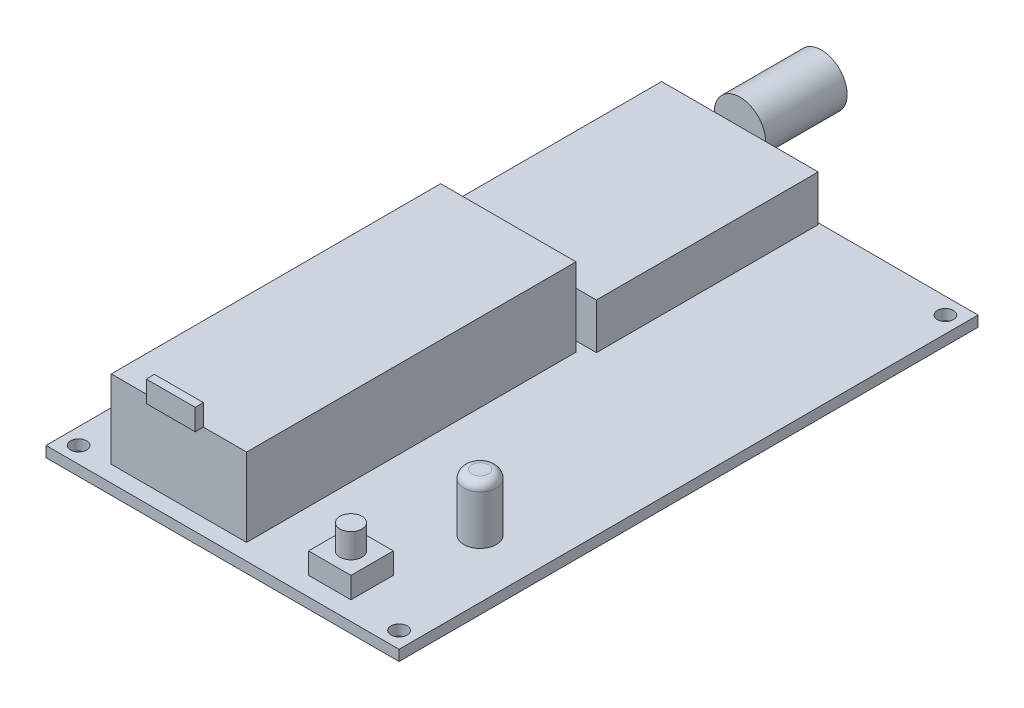
SolidWorks part; units mm, degrees
ref_plane "Front Plane" through (0, 0, 0) normal (0, 0, 1) x (1, 0, 0)
ref_plane "Top Plane" through (0, 0, 0) normal (0, 1, 0) x (1, 0, 0)
ref_plane "Right Plane" through (0, 0, 0) normal (1, 0, 0) x (0, 0, -1)
sketch "Sketch1" plane through (0, 0, 0) normal (0, 1, 0) x (1, 0, 0)
  line L1 (0, 0) -> (54.991, 0)
  line L2 (0, 0) -> (0, 90.17)
  line L3 (0, 90.17) -> (54.991, 90.17)
  line L4 (54.991, 0) -> (54.991, 90.17)
  dimension "D1" = 54.991
  dimension "D2" = 90.17
extrude "Board" add sketch "Sketch1" along normal blind 1.651
sketch "Sketch2" plane through (0, 1.651, 0) normal (0, 1, 0) x (1, 0, 0)
  line L0 (0, 0) -> (54.991, 0) construction
  line L1 (7.62, 2.54) -> (28.702, 2.54)
  line L2 (7.62, 2.54) -> (7.62, 53.848)
  line L3 (7.62, 53.848) -> (28.702, 53.848)
  line L4 (28.702, 2.54) -> (28.702, 53.848)
  line L5 (37.973, 9.525) -> (44.577, 9.525)
  line L6 (37.973, 9.525) -> (37.973, 2.921)
  line L7 (37.973, 2.921) -> (44.577, 2.921)
  line L8 (44.577, 9.525) -> (44.577, 2.921)
  line L9 (54.991, 0) -> (54.991, 90.17) construction
  line L10 (0, 90.17) -> (0, 0) construction
  line L12 (5.969, 89.916) -> (30.353, 89.916)
  line L13 (5.969, 89.916) -> (5.969, 55.372)
  line L14 (5.969, 55.372) -> (30.353, 55.372)
  line L15 (30.353, 89.916) -> (30.353, 55.372)
  point P18 (18.161, 55.372)
  point P19 (18.161, 53.848)
  point P20 (0, 0)
  dimension "D1" = 21.082
  dimension "D2" = 51.308
  dimension "D3" = 6.604
  dimension "D4" = 6.604
  dimension "D5" = 9.525
  dimension "D6" = 17.018
  dimension "D7" = 2.54
  dimension "D8" = 7.62
  dimension "D9" = 24.384
  dimension "D10" = 34.544
  dimension "D11" = 1.524
extrude "RPI" add sketch "Sketch2" along normal blind 12.192 contours L1 L4 L3 L2 region at (18.161, 1.651, -28.194)
extrude "Button Base" add sketch "Sketch2<3>" along normal blind 3.302 contours L6 L7 L8 L5
sketch "Sketch2<3>" plane through (0, 1.651, 0) normal (0, 1, 0) x (1, 0, 0) same geometry as "Sketch2"
extrude "Zigbee" add sketch "Sketch2<4>" along normal blind 7.112 contours L13 L14 L15 L12
sketch "Sketch2<4>" plane through (0, 1.651, 0) normal (0, 1, 0) x (1, 0, 0) same geometry as "Sketch2"
sketch "Sketch3" plane through (0, 4.953, 0) normal (0, 1, 0) x (1, 0, 0)
  line L0 (37.973, 9.525) -> (44.577, 9.525) construction
  line L1 (37.973, 9.525) -> (37.973, 2.921) construction
  circle A0 centre (41.275, 6.223) radius 1.7145
  point P2 (41.275, 9.525)
  point P3 (37.973, 6.223)
  point P6 (0, 0)
  dimension "D1" = 3.429
extrude "Button" add sketch "Sketch3" along normal blind 3.81
sketch "Sketch4" plane through (0, 1.651, 0) normal (0, 1, 0) x (1, 0, 0)
  circle A0 centre (45.9084, 21.7018) radius 2.54
  dimension "D1" = 5.08
extrude "LED" add sketch "Sketch4" along normal blind 8.89
fillet "Fillet1" radius 1.27 1 edges at (45.9084, 10.541, -19.1618)
sketch "Sketch5" plane through (0, 0, -2.54) normal (0, 0, 1) x (1, 0, 0)
  line L0 (7.62, 13.843) -> (28.702, 13.843) construction
  line L1 (21.971, 13.843) -> (14.351, 13.843)
  line L2 (21.971, 13.843) -> (21.971, 17.145)
  line L3 (21.971, 17.145) -> (14.351, 17.145)
  line L4 (14.351, 13.843) -> (14.351, 17.145)
  point P6 (18.161, 13.843)
  point P7 (18.161, 17.145)
  point P8 (0, 0)
  dimension "D1" = 7.62
  dimension "D2" = 3.302
extrude "PI Plug" add sketch "Sketch5" along normal blind 1.27 separate body
sketch "Sketch6" plane through (0, 0, -89.916) normal (0, 0, -1) x (-1, 0, 0)
  line L0 (-5.969, 8.763) -> (-30.353, 8.763) construction
  circle A0 centre (-18.161, 8.763) radius 4.0005
  point P2 (-18.161, 8.763)
  point P3 (-18.161, 8.763)
  dimension "D1" = 8.001
extrude "Boss-Extrude8" add sketch "Sketch6" along normal blind 12.7
sketch "Sketch7" plane through (0, 1.651, 0) normal (0, 1, 0) x (1, 0, 0)
  line L0 (54.991, 90.17) -> (0, 90.17) construction
  line L1 (0, 90.17) -> (0, 0) construction
  line L2 (54.991, 0) -> (54.991, 90.17) construction
  line L3 (0, 0) -> (54.991, 0) construction
  circle A0 centre (2.54, 87.63) radius 1.25
  circle A1 centre (2.54, 2.54) radius 1.25
  circle A2 centre (52.451, 2.54) radius 1.25
  circle A3 centre (52.451, 87.63) radius 1.25
  point P8 (2.0417, 88.0746)
  dimension "D1" = 2.5
  dimension "D2" = 2.54
  dimension "D3" = 2.54
  dimension "D4" = 2.54
  dimension "D5" = 2.54
  dimension "D6" = 2.54
  dimension "D7" = 2.54
  dimension "D8" = 2.54
  dimension "D9" = 2.54
extrude "Screw Holes" cut sketch "Sketch7" against normal through all
